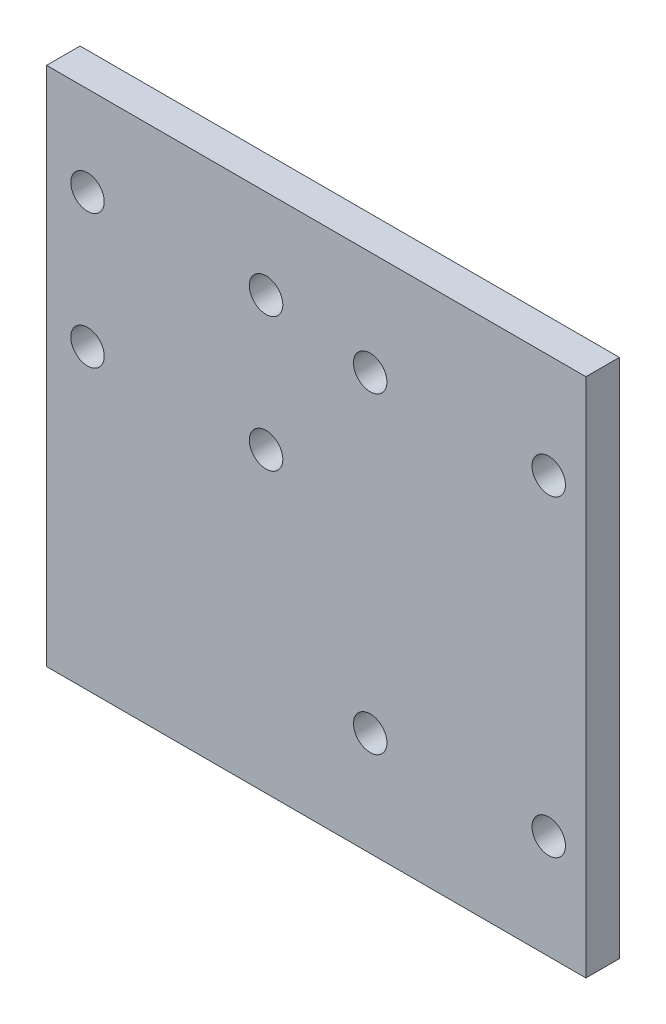
SolidWorks part; units mm, degrees
ref_plane "Front Plane" through (0, 0, 0) normal (0, 0, 1) x (1, 0, 0)
ref_plane "Top Plane" through (0, 0, 0) normal (0, 1, 0) x (1, 0, 0)
ref_plane "Right Plane" through (0, 0, 0) normal (1, 0, 0) x (0, 0, -1)
sketch "Sketch1" plane through (0, 0, 0) normal (0, 0, 1) x (1, 0, 0)
  line L0 (-5.2261, -963.3831) -> (-5.2261, 49036.6169) construction
  line L1 (-40.2261, 36.6169) -> (32.2739, 36.6169)
  line L2 (-40.2261, 36.6169) -> (-40.2261, -33.3831)
  line L3 (-40.2261, -33.3831) -> (32.2739, -33.3831)
  line L4 (32.2739, 36.6169) -> (32.2739, -33.3831)
  line L10 (-1040.2261, 1.6169) -> (48959.7739, 1.6169) construction
  circle A0 centre (-34.7261, 24.6169) radius 2.25
  circle A1 centre (-10.7261, 24.6169) radius 2.25
  circle A2 centre (-10.7261, 6.6169) radius 2.25
  circle A3 centre (-34.7261, 6.6169) radius 2.25
  circle A5 centre (3.2739, -19.3831) radius 2.25
  circle A6 centre (3.2739, 22.6169) radius 2.25
  circle A7 centre (27.2739, -19.3831) radius 2.25
  circle A8 centre (27.2739, 22.6169) radius 2.25
base flange "Base-Flange1" sketch "Sketch1" thickness 4.5 reverse thickness direction no parameters "D1"=1.5
sketch "Bend-Lines5" [suppressed] plane through (0, 0, 0) normal (0, 1, 0) x (1, 0, 0)
sketch "Bounding-Box5" [suppressed] plane through (0, 0, 0) normal (0, 1, 0) x (1, 0, 0)
sheet metal parameters "Sheet-Metal4" thickness 4.5 parameters "D1"=1.5
flat pattern "Flat-Pattern4" [suppressed]
sketch "Bend-Lines6" plane through (0, 0, 0) normal (0, 1, 0) x (1, 0, 0)
sketch3d "Bounding-Box6" [suppressed]
  line L0 (-40.2261, -33.3831, 0) -> (32.2739, -33.3831, 0) construction
  line L1 (-40.2261, 36.6169, 0) -> (32.2739, 36.6169, 0) construction
  line L2 (-40.2261, -33.3831, 0) -> (-40.2261, 36.6169, 0) construction
  line L3 (32.2739, -33.3831, 0) -> (32.2739, 36.6169, 0) construction
